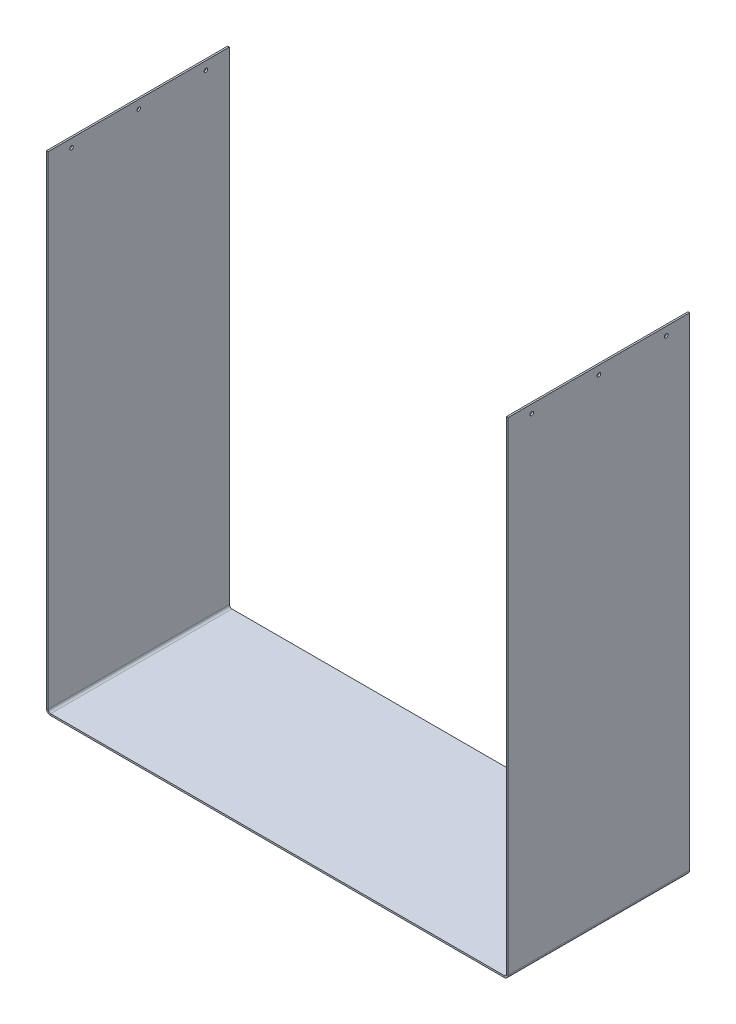
SolidWorks part; units mm, degrees
note: The reader was unsure of these and kept them because the rebuilt part matched: flange length of "Odgięcie krawędzi1".
ref_plane "Płaszczyzna przednia" through (0, 0, 0) normal (0, 0, 1) x (1, 0, 0)
ref_plane "Płaszczyzna górna" through (0, 0, 0) normal (0, 1, 0) x (1, 0, 0)
ref_plane "Płaszczyzna prawa" through (0, 0, 0) normal (1, 0, 0) x (0, 0, -1)
sketch "Szkic1" plane through (0, 0, 0) normal (0, 1, 0) x (1, 0, 0)
  line L1 (-273, -108) -> (273, -108)
  line L2 (-273, -108) -> (-273, 108)
  line L3 (-273, 108) -> (273, 108)
  line L4 (273, -108) -> (273, 108)
  line L5 (-273, -108) -> (273, 108) construction
  line L6 (-273, 108) -> (273, -108) construction
  point P0 (0, 0)
  dimension "D1" = 546
  dimension "D2" = 216
base flange "Odgięcie bazowe1" sketch "Szkic1" thickness 2 reverse thickness direction no parameters "D1"=0.7366
edge flange "Odgięcie krawędzi1" sketch "Szkic10" flange profiles "Szkic10", "Szkic11" flange angle 90 flange length 580 bend radius 3 thickness 2 parameters "D6"=10, "D8"=1
sketch "Szkic10" plane through (-273, 0, 0) normal (-1, 0, 0) x (0, 0, 1)
  line L2 (-108, 0) -> (-108, 578)
  line L3 (-108, 578) -> (108, 578)
  line L4 (108, 578) -> (108, 0)
  line L7 (-108, 0) -> (108, 0) construction
  line L8 (-108, 0) -> (108, 0)
sketch "Szkic11" plane through (273, 0, 0) normal (1, 0, 0) x (0, 0, -1)
  line L0 (-108, 0) -> (108, 0) construction
  line L1 (-108, 0) -> (108, 0)
  line L2 (-108, 0) -> (-108, 578)
  line L3 (-108, 578) -> (108, 578)
  line L4 (108, 578) -> (108, 0)
bend "Zgięcie krawędziowe1" bend radius 3 bend angle 90 parameters "D5"=1
bend "Zgięcie krawędziowe2" bend radius 3 bend angle 90 parameters "D5"=2
sketch "Szkic12" plane through (-275, 0, 0) normal (-1, 0, 0) x (0, 0, 1)
  line L0 (0, 578) -> (0, 0) construction
  line L1 (108, 578) -> (-108, 578) construction
  circle A0 centre (0, 568) radius 2.1
  circle A1 centre (80, 568) radius 2.1
  circle A2 centre (-80, 568) radius 2.1
  dimension "D1" = 10
  dimension "D2" = 4.2
  dimension "D3" = 2
extrude "Wytnij-wyciągnięcie1" cut sketch "Szkic12" against normal through all
sketch "Linie zgięcia1" [suppressed] plane through (0, 0, 0) normal (0, 1, 0) x (1, 0, 0)
sketch "Ramka-graniczna1" [suppressed] plane through (0, 0, 0) normal (0, 1, 0) x (1, 0, 0)
sheet metal parameters "Arkusz blachy1" thickness 2 parameters "D1"=0.7366
flat pattern "Rozłożony model1" [suppressed]
sketch "Linie zgięcia2" plane through (0, 0, 0) normal (0, 1, 0) x (1, 0, 0)
sketch3d "Ramka-graniczna2" [suppressed]
  line L0 (-210, 150, 0) -> (210, 150, 0) construction
  line L1 (-210, -150, 0) -> (210, -150, 0) construction
  line L2 (-210, 150, 0) -> (-210, -150, 0) construction
  line L3 (210, 150, 0) -> (210, -150, 0) construction
sheet metal parameters "Arkusz blachy2" thickness 2 parameters "D1"=0.7366
flat pattern "Rozłożony model1"
sketch "Linie zgięcia2" plane through (0, 0, 0) normal (0, 1, 0) x (1, 0, 0)
  line L0 (273.1416, -108) -> (273.1416, 108) construction
  line L1 (-273.1416, 108) -> (-273.1416, -108) construction
  line L2 (273.1416, -108) -> (273.1416, 108) construction
  line L3 (-273.1416, 108) -> (-273.1416, -108) construction
sketch3d "Ramka-graniczna2" [suppressed]
  line L0 (851.2832, 108, 0) -> (-851.2832, 108, 0) construction
  line L1 (851.2832, -108, 0) -> (-851.2832, -108, 0) construction
  line L2 (851.2832, 108, 0) -> (851.2832, -108, 0) construction
  line L3 (-851.2832, 108, 0) -> (-851.2832, -108, 0) construction
bend of the flat pattern "Rozłożone-<Zgięcie krawędziowe1>1"
bend of the flat pattern "Rozłożone-<Zgięcie krawędziowe2>1"
sheet metal parameters "Arkusz blachy3" thickness 2 parameters "D1"=0.7366
flat pattern "Rozłożony model1"
sketch "Linie zgięcia2" plane through (0, 0, 0) normal (0, 1, 0) x (1, 0, 0)
  line L0 (273.1416, -108) -> (273.1416, 108) construction
  line L1 (-273.1416, 108) -> (-273.1416, -108) construction
  line L2 (273.1416, -108) -> (273.1416, 108) construction
  line L3 (-273.1416, 108) -> (-273.1416, -108) construction
sketch3d "Ramka-graniczna2" [suppressed]
  line L0 (851.2832, 108, 0) -> (-851.2832, 108, 0) construction
  line L1 (851.2832, -108, 0) -> (-851.2832, -108, 0) construction
  line L2 (851.2832, 108, 0) -> (851.2832, -108, 0) construction
  line L3 (-851.2832, 108, 0) -> (-851.2832, -108, 0) construction
bend of the flat pattern "Rozłożone-<Zgięcie krawędziowe1>1"
bend of the flat pattern "Rozłożone-<Zgięcie krawędziowe2>1"
